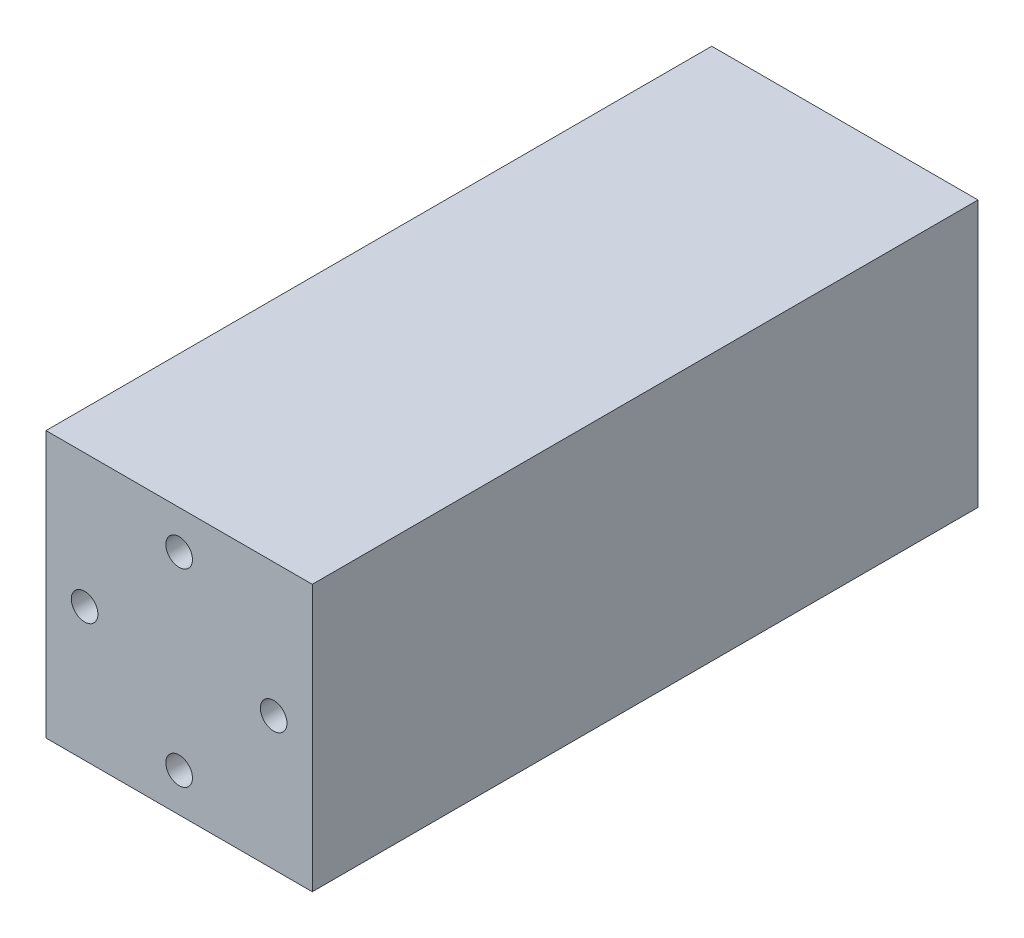
SolidWorks part; units mm, degrees
ref_plane "前视基准面" through (0, 0, 0) normal (0, 0, 1) x (1, 0, 0)
ref_plane "上视基准面" through (0, 0, 0) normal (0, 1, 0) x (1, 0, 0)
ref_plane "右视基准面" through (0, 0, 0) normal (1, 0, 0) x (0, 0, -1)
other "Configuration Table"
sketch "草图1" plane through (0, 0, 0) normal (0, 0, 1) x (1, 0, 0)
  line L1 (-8.8, -8.8) -> (8.8, -8.8)
  line L2 (-8.8, -8.8) -> (-8.8, 8.8)
  line L3 (-8.8, 8.8) -> (8.8, 8.8)
  line L4 (8.8, -8.8) -> (8.8, 8.8)
  line L5 (-8.8, -8.8) -> (8.8, 8.8) construction
  line L6 (-8.8, 8.8) -> (8.8, -8.8) construction
  line L7 (-10, -10) -> (10, -10)
  line L8 (-10, -10) -> (-10, 10)
  line L9 (-10, 10) -> (10, 10)
  line L10 (10, -10) -> (10, 10)
  line L11 (-10, -10) -> (10, 10) construction
  line L12 (-10, 10) -> (10, -10) construction
  circle A0 centre (0, 7.1) radius 1.7
  circle A1 centre (-7.1, 0) radius 1.7
  circle A2 centre (0, -7.1) radius 1.7
  circle A3 centre (7.1, 0) radius 1.7
  circle A4 centre (-7.1, 0) radius 1
  circle A5 centre (0, 7.1) radius 1
  circle A6 centre (7.1, 0) radius 1
  circle A7 centre (0, -7.1) radius 1
  point P0 (0, 0)
  point P16 (0, 0)
  dimension "D2" = 3.4
  dimension "D4" = 2
  dimension "D1" = 17.6
  dimension "D3" = 20
extrude "凸台-拉伸1" add sketch "草图1" along normal blind 50 contours L9 L10 L7 L8
extrude "切除-拉伸1" cut sketch "草图1<3>" along normal blind 3 contours A5 | A4 | A6 | A7
sketch "草图1<3>" plane through (0, 0, 0) normal (0, 0, 1) x (1, 0, 0) same geometry as "草图1"
extrude "切除-拉伸2" cut sketch "草图1<4>" against normal blind 3 from surface contours A5 | A4 | A6 | A7 starting at face at (0, 0, 50)
sketch "草图1<4>" plane through (0, 0, 0) normal (0, 0, 1) x (1, 0, 0) same geometry as "草图1"
